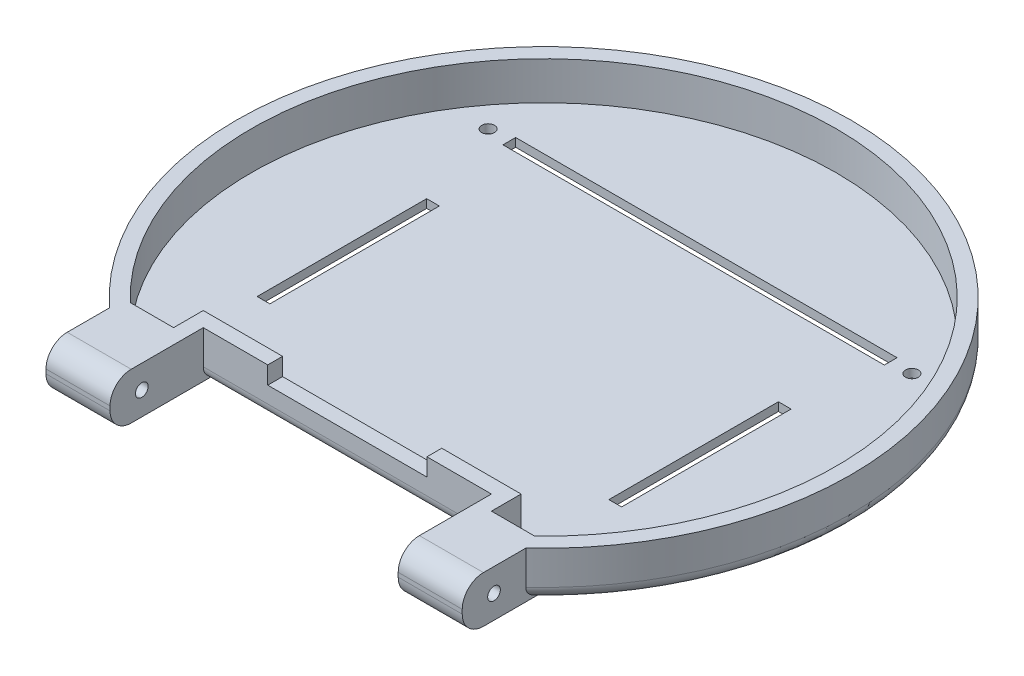
SolidWorks part; units mm, degrees
ref_plane "Front Plane" through (0, 0, 0) normal (0, 0, 1) x (1, 0, 0)
ref_plane "Top Plane" through (0, 0, 0) normal (0, 1, 0) x (1, 0, 0)
ref_plane "Right Plane" through (0, 0, 0) normal (1, 0, 0) x (0, 0, -1)
sketch "Sketch1" plane through (0, 0, 0) normal (0, 1, 0) x (1, 0, 0)
  line L0 (-0.3609, 67.0955) -> (-0.3609, 70.5955) construction
  line L1 (-47.7229, -51.7385) -> (-37.5, -51.7385)
  line L2 (-49.1084, -55.2385) -> (-34, -55.2385)
  line L3 (-50, 34.9766) -> (-48.5, 34.9766) construction
  line L4 (-45, 36.4766) -> (45, 36.4766)
  line L5 (-45, 36.4766) -> (-45, 33.4766)
  line L6 (-45, 33.4766) -> (45, 33.4766)
  line L7 (45, 36.4766) -> (45, 33.4766)
  line L8 (0, 0) -> (0, 40.1699) construction
  line L9 (-45, 34.9766) -> (45, 34.9766) construction
  line L10 (48.5, 34.9766) -> (50, 34.9766) construction
  line L11 (34, -55.2385) -> (49.1084, -55.2385)
  line L12 (-43, 13.4766) -> (-40, 13.4766)
  line L13 (-43, 13.4766) -> (-43, -26.5234)
  line L14 (-43, -26.5234) -> (-40, -26.5234)
  line L15 (-40, 13.4766) -> (-40, -26.5234)
  line L16 (40, 13.4766) -> (43, 13.4766)
  line L17 (40, 13.4766) -> (40, -26.5234)
  line L18 (40, -26.5234) -> (43, -26.5234)
  line L19 (43, 13.4766) -> (43, -26.5234)
  line L20 (-28.5453, -55.2385) -> (-34, -55.2385)
  line L21 (-37.5, -51.7385) -> (-37.5, -44.7397)
  line L22 (-37.5, -44.7397) -> (37.5, -44.7397)
  line L23 (37.5, -51.7385) -> (37.5, -44.7397)
  line L25 (-34, -55.2385) -> (-34, -48.2397)
  line L26 (-34, -48.2397) -> (34, -48.2397)
  line L27 (34, -55.2385) -> (34, -48.2397)
  line L28 (34, -55.2385) -> (29.2788, -55.2385)
  line L29 (37.5, -51.7385) -> (47.7229, -51.7385)
  line L30 (0, 0) -> (0, -66.3998) construction
  arc A0 (49.1084, -55.2385) -> (-49.1084, -55.2385) centre (0, -1.9036) ccw
  circle A1 centre (-50, 34.9766) radius 1.5
  circle A2 centre (50, 34.9766) radius 1.5
  circle A3 centre (25.7788, -40.8842) radius 1.5
  circle A4 centre (-25.7788, -40.8842) radius 1.5
  arc A5 (47.7229, -51.7385) -> (-47.7229, -51.7385) centre (0, -1.9036) ccw
  point P14 (5.2809, -60.0397)
  point P16 (0, -55.2385)
  dimension "D1" = 145
  dimension "D2" = 138
  dimension "D4" = 3
  dimension "D3" = 3.5
  dimension "D5" = 3
  dimension "D6" = 1.5
  dimension "D7" = 50
  dimension "D8" = 45
  dimension "D9" = 90
  dimension "D10" = 3
  dimension "D11" = 3
  dimension "D12" = 40
  dimension "D13" = 40
  dimension "D14" = 40
  dimension "D15" = 40
  dimension "D16" = 20
  dimension "D17" = 20
  dimension "D18" = 3.5
  dimension "D19" = 3.5
  dimension "D20" = 3.5
  dimension "D21" = 75
  dimension "D22" = 37.5
extrude "Boss-Extrude1" add sketch "Sketch1" along normal blind 2 contours L1 A5 L4 L7 L6 L5 L12 L15 L14 L13 L16 L19 L18 L17 A1 A2 A3 A4 | L2 A0 A5 L1 region at (0, 0, -5.0576) region at (0, 0, -68.6765)
extrude "Boss-Extrude2" add sketch "Sketch1<3>" along normal blind 11 contours L2 A0 A5 L1 region at (0, 0, -68.6765)
sketch "Sketch1<3>" plane through (0, 0, 0) normal (0, 1, 0) x (1, 0, 0) same geometry as "Sketch1"
sketch "Sketch2" plane through (0, 0, 0) normal (0, -1, 0) x (-1, 0, 0)
  line L0 (32.7, -58.8076) -> (-32.7, -58.8076) construction
  line L1 (0, -48.2397) -> (0, -73.4465) construction
  line L2 (34, -48.2397) -> (-34, -48.2397) construction
  dimension "D1" = 65.4
  dimension "D2" = 32.7
sketch "Sketch3" plane through (0, 0, 55.2385) normal (0, 0, 1) x (1, 0, 0)
  line L0 (34, 0) -> (49.1084, 0) construction
  line L1 (49.1084, 0) -> (49.1084, 11) construction
  line L2 (49.1084, 11) -> (34, 11) construction
  line L3 (34, 11) -> (34, 0) construction
  line L4 (-49.1084, 0) -> (-34, 0) construction
  line L5 (-34, 0) -> (-34, 11) construction
  line L6 (-34, 11) -> (-49.1084, 11) construction
  line L7 (-49.1084, 11) -> (-49.1084, 0) construction
  line L8 (34, 0) -> (49.1084, 0)
  line L9 (49.1084, 0) -> (49.1084, 11)
  line L10 (49.1084, 11) -> (34, 11)
  line L11 (34, 11) -> (34, 0)
  line L12 (-49.1084, 0) -> (-34, 0)
  line L13 (-34, 0) -> (-34, 11)
  line L14 (-34, 11) -> (-49.1084, 11)
  line L15 (-49.1084, 11) -> (-49.1084, 0)
extrude "Boss-Extrude3" add sketch "Sketch3" along normal blind 15
sketch "Sketch4" plane through (-49.1084, 0, 0) normal (-1, 0, 0) x (0, 0, 1)
  line L0 (70.2385, 5.5) -> (55.2385, 5.5) construction
  line L1 (70.2385, 11) -> (70.2385, 0) construction
  line L2 (55.2385, 11) -> (55.2385, 0) construction
  line L3 (62.7385, 0) -> (62.7385, 5.5) construction
  line L4 (48.2397, 0) -> (73.4465, 0) construction
  circle A0 centre (62.7385, 5.5) radius 1.5
  point P8 (0, 0)
  point P9 (0, 0)
  point P10 (0, 0)
  point P11 (0, 0)
  point P12 (65.3618, 3.2311)
  point P14 (62.7385, 4.0018)
  point P17 (62.7125, 3.472)
  point P18 (62.7385, 5)
  dimension "D1" = 3
extrude "Cut-Extrude1" cut sketch "Sketch4" against normal blind 115
fillet "Fillet2" radius 3 2 edges at (0, 0, 48.2397) (0, 0, -70.5964)
fillet "Fillet3" radius 5 4 edges at (41.5542, 0, 70.2385) (41.5542, 11, 70.2385) (-41.5542, 0, 70.2385) (-41.5542, 11, 70.2385)
sketch "Sketch5" plane through (0, 0, 48.2397) normal (0, 0, 1) x (1, 0, 0)
  line L0 (-34, 11) -> (34, 11) construction
  line L1 (-18.7819, 15.1463) -> (18.7819, 15.1463)
  line L2 (-18.7819, 15.1463) -> (-18.7819, 6.8537)
  line L3 (-18.7819, 6.8537) -> (18.7819, 6.8537)
  line L4 (18.7819, 15.1463) -> (18.7819, 6.8537)
  line L5 (-18.7819, 15.1463) -> (18.7819, 6.8537) construction
  line L6 (-18.7819, 6.8537) -> (18.7819, 15.1463) construction
  point P0 (0, 11)
extrude "Cut-Extrude2" cut sketch "Sketch5" against normal blind 10
